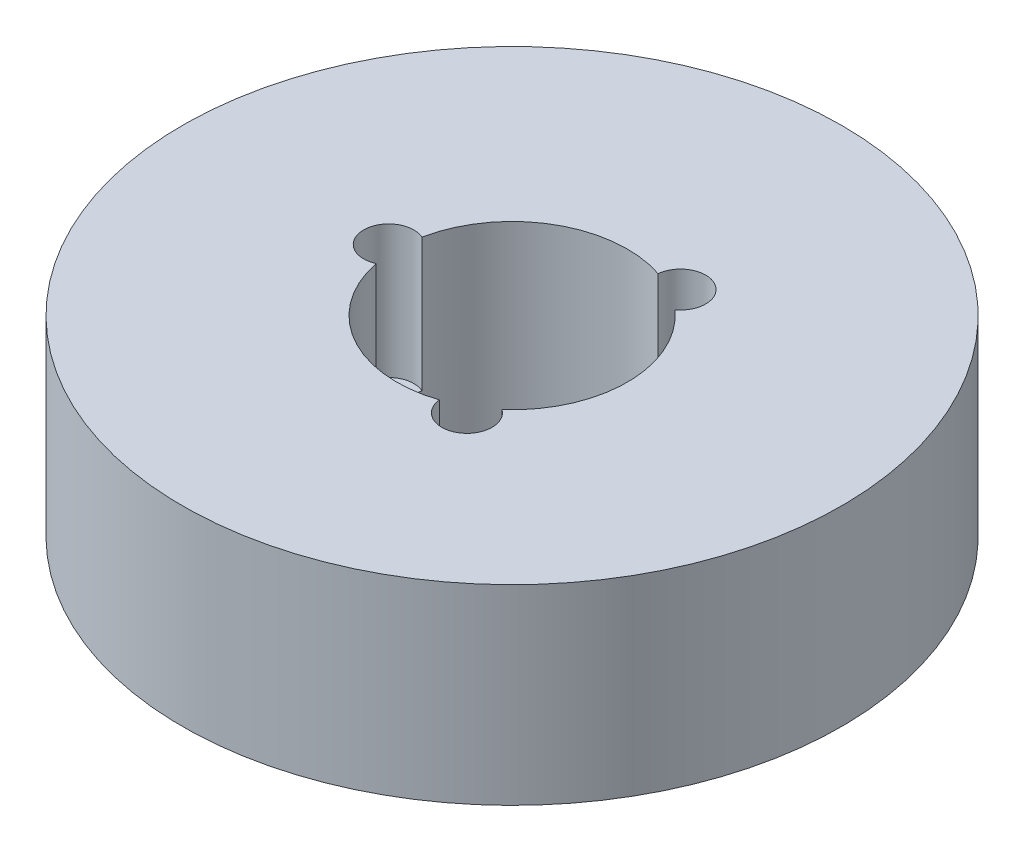
SolidWorks part; units mm, degrees
ref_plane "Front Plane" through (0, 0, 0) normal (0, 0, 1) x (1, 0, 0)
ref_plane "Top Plane" through (0, 0, 0) normal (0, 1, 0) x (1, 0, 0)
ref_plane "Right Plane" through (0, 0, 0) normal (1, 0, 0) x (0, 0, -1)
sketch "Sketch1" plane through (0, 0, 0) normal (0, 1, 0) x (1, 0, 0)
  circle A0 centre (0, 0) radius 50
  dimension "FLANGE_OD" = 100
extrude "Boss-Extrude1" add sketch "Sketch1" along normal blind 29
sketch "Sketch2" plane through (0, 0, 0) normal (0, 1, 0) x (1, 0, 0)
  circle A0 centre (0, 0) radius 17.5
  dimension "BORE_D" = 35
extrude "Cut-Extrude1" cut sketch "Sketch2" along normal through all
sketch "Sketch3" plane through (0, 29, 0) normal (0, 1, 0) x (1, 0, 0)
  circle A0 centre (0, 0) radius 18.7114 construction
  circle A1 centre (-18.7114, 0) radius 3.812
  dimension "BOLT_D" = 7.6241
  dimension "BOLT_PCD" = 37.4228
extrude "Cut-Extrude2" cut sketch "Sketch3" against normal blind 20.1885
pattern_circular "CirPattern1" count 3 over 360 about axis through (0, 0, 0) along (0, 1, 0) of "Cut-Extrude2"
